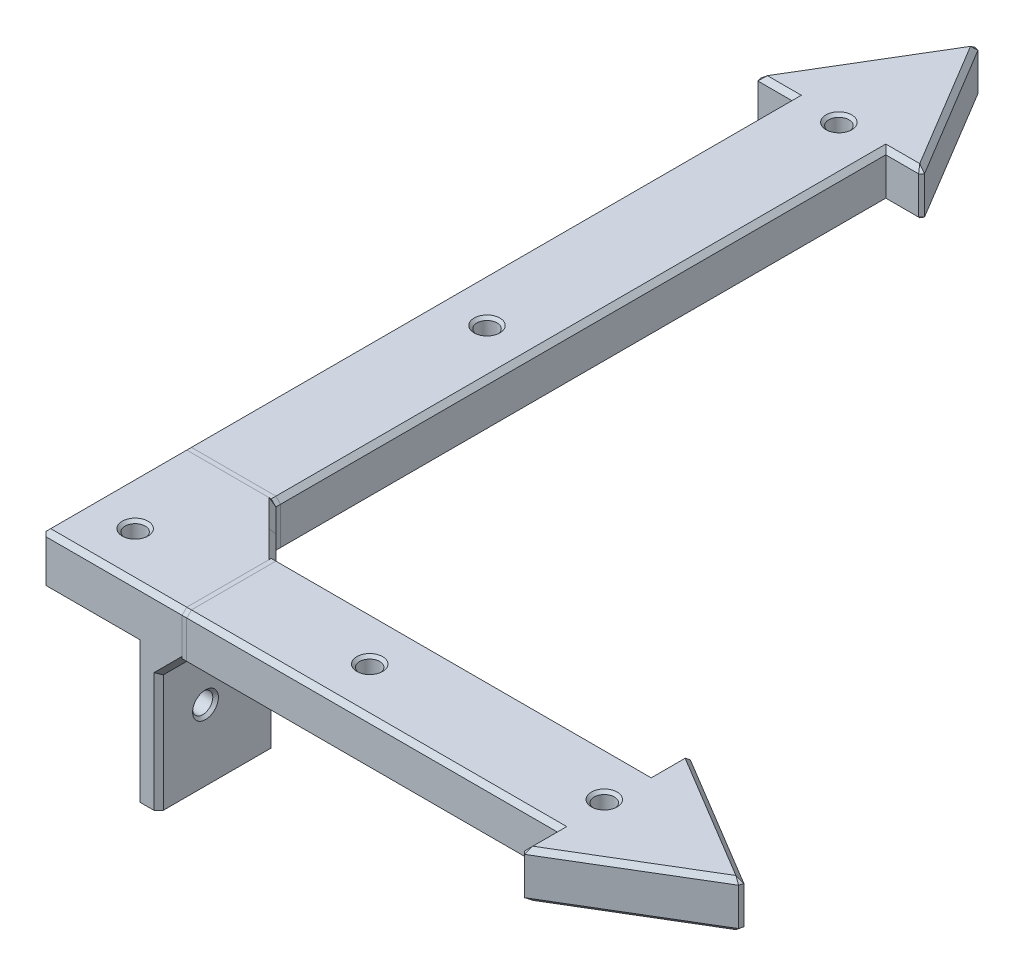
SolidWorks part; units mm, degrees
note: The reader was unsure of these and kept them because the rebuilt part matched: shared geometry of "Sketch3<3>", "Sketch9<2>".
ref_plane "Front Plane" through (0, 0, 0) normal (0, 0, 1) x (1, 0, 0)
ref_plane "Top Plane" through (0, 0, 0) normal (0, 1, 0) x (1, 0, 0)
ref_plane "Right Plane" through (0, 0, 0) normal (1, 0, 0) x (0, 0, -1)
sketch "Sketch1" plane through (0, 0, 0) normal (0, 1, 0) x (1, 0, 0)
  line L0 (0, 0) -> (100, 0) construction
  line L1 (0, 0) -> (0, 150) construction
  line L2 (10, 150) -> (10, 10)
  line L3 (10, 10) -> (100, 10)
  line L4 (100, -10) -> (-10, -10)
  line L5 (-10, -10) -> (-10, 150)
  line L6 (0, 150) -> (10, 150) construction
  line L7 (0, 150) -> (-10, 150) construction
  line L8 (100, 10) -> (100, 0) construction
  line L9 (100, 0) -> (100, -10) construction
  line L10 (0, 150) -> (0, 180) construction
  line L11 (0, 180) -> (18, 150)
  line L12 (18, 150) -> (10, 150)
  line L13 (-10, 150) -> (-18, 150)
  line L14 (-18, 150) -> (0, 180)
  line L15 (100, 0) -> (130, 0) construction
  line L16 (130, 0) -> (100, 18)
  line L17 (100, 18) -> (100, 10)
  line L18 (100, -10) -> (100, -18)
  line L19 (100, -18) -> (130, 0)
  dimension "D1" = 150
  dimension "D2" = 20
  dimension "D3" = 30
  dimension "D4" = 36
  dimension "D5" = 100
extrude "Boss-Extrude1" add sketch "Sketch1" along normal blind 10
sketch "Sketch2" plane through (0, 10, 0) normal (0, 1, 0) x (1, 0, 0)
  line L0 (0, 150) -> (0, 0) construction
  line L1 (0, 0) -> (100, 0) construction
  circle A0 centre (0, 150) radius 2.15
  circle A1 centre (100, 0) radius 2.15
  circle A2 centre (0, 0) radius 2.15
  circle A3 centre (0, 75) radius 2.15
  circle A4 centre (50, 0) radius 2.15
  dimension "D1" = 4.3
extrude "Cut-Extrude1" cut sketch "Sketch2" against normal through all
sketch "Sketch3" plane through (0, 0, 0) normal (0, -1, 0) x (1, 0, 0)
  line L5 (10, 10) -> (15, 10)
  line L16 (-10, 10) -> (10, 10) construction
  line L21 (-10, 10) -> (-10, -10) construction
  line L22 (-10, -10) -> (10, -10) construction
  line L23 (10, 10) -> (10, -10) construction
  line L24 (-10, 10) -> (10, -10) construction
  line L25 (-10, -10) -> (10, 10) construction
  line L26 (-10, 10) -> (100, 10) construction
  line L27 (15, 10) -> (15, -15)
  line L28 (15, -15) -> (-10, -15)
  line L29 (-10, -150) -> (-10, 10) construction
  line L30 (-10, -15) -> (-10, -10)
  line L31 (-10, -10) -> (10, -10)
  line L32 (10, -10) -> (10, 10)
  point P0 (0, 0)
  dimension "D1" = 5
extrude "Boss-Extrude5" add sketch "Sketch3" against normal up to surface (10 mm away) up to face at (0, 10, -147.85)
extrude "Boss-Extrude6" add sketch "Sketch3<3>" along normal blind 30
sketch "Sketch3<3>" plane through (0, 0, 0) normal (0, -1, 0) x (1, 0, 0) same geometry as "Sketch3"
sketch "Sketch4" plane through (0, 0, -10) normal (0, 0, 1) x (1, 0, 0)
  line L0 (-10, 0) -> (10, -30) construction
  circle A0 centre (0, -15) radius 2.15
  dimension "D1" = 4.3
extrude "Cut-Extrude2" cut sketch "Sketch4" against normal through all
sketch "Sketch5" plane through (10, 0, 0) normal (-1, 0, 0) x (0, 0, 1)
  line L0 (-10, 0) -> (10, -30) construction
  circle A0 centre (0, -15) radius 2.15
  dimension "D1" = 4.3
extrude "Cut-Extrude3" cut sketch "Sketch5" against normal through all
sketch "Sketch6" plane through (0, 0, 0) normal (0, -1, 0) x (1, 0, 0)
  circle A0 centre (0, 0) radius 5
  dimension "D1" = 10
extrude "Cut-Extrude4" cut sketch "Sketch6" against normal offset from surface (6 mm away) 4 up to face at (40, 10, -57.8571)
chamfer "Chamfer1" distance 5 angle 45 6 edges at (0, 0, -15) (12.5, 10, -15) (15, 10, -12.5) (10, 5, -15) (15, 5, -10) (15, 0, 0)
sketch "Sketch9" plane through (0, 10, 0) normal (0, 1, 0) x (1, 0, 0)
  line L0 (-10, 150) -> (-10, -10) construction
  line L1 (10, 20) -> (-10, 20)
  line L2 (10, 20) -> (10, 21)
  line L3 (10, 21) -> (-10, 21)
  line L4 (-10, 20) -> (-10, 21)
  line L5 (-10, -10) -> (100, -10) construction
  line L6 (20, 10) -> (21, 10)
  line L7 (20, 10) -> (20, -10)
  line L8 (20, -10) -> (21, -10)
  line L9 (21, 10) -> (21, -10)
  dimension "D1" = 1
extrude "Cut-Extrude5" cut sketch "Sketch9" against normal through all
extrude "Boss-Extrude7" add sketch "Sketch9<2>" against normal up to surface (10 mm away) separate body up to face at (0, 0, -147.85)
sketch "Sketch9<2>" plane through (0, 10, 0) normal (0, 1, 0) x (1, 0, 0) same geometry as "Sketch9"
chamfer "Chamfer2" distance 1 angle 45 15 edges at (-18, 5, -150) (-10, 0, -85.5) (-14, 0, -150) (-9, 0, -165) (9, 0, -165) (14, 0, -150) (10, 0, -85.5) (-10, 10, -85.5) (-14, 10, -150) (-9, 10, -165) (9, 10, -165) (14, 10, -150) (10, 10, -85.5) (18, 5, -150) (0, 5, -180)
chamfer "Chamfer3" distance 1 angle 45 3 edges at (10, 0, -20.5) (10, 10, -20.5) (-10, 10, -20.5)
chamfer "Chamfer4" distance 1 angle 45 4 edges at (5, 10, 10) (-10, 10, -5) (17.5, 10, -12.5) (12.5, 10, -17.5)
chamfer "Chamfer5" distance 1 angle 45 4 edges at (20.5, 0, -10) (20.5, 0, 10) (20.5, 10, -10) (20.5, 10, 10)
chamfer "Chamfer6" distance 1 angle 45 15 edges at (100, 0, -14) (100, 5, -18) (115, 0, -9) (130, 5, 0) (115, 0, 9) (100, 5, 18) (100, 0, 14) (60.5, 10, 10) (100, 10, 14) (115, 10, 9) (115, 10, -9) (100, 10, -14) (60.5, 10, -10) (60.5, 0, -10) (60.5, 0, 10)
chamfer "Chamfer7" distance 1 angle 45 8 edges at (-10, -2.5, -17.5) (-10, -15, -10) (17.5, -2.5, 10) (15, -17.5, 10) (-10, -17.5, -15) (15, -17.5, -15) (10, -15, 10) (-10, 4.5, 10)
sketch "Sketch10" plane through (0, 0, 0) normal (0, -1, 0) x (1, 0, 0)
  circle A0 centre (100, 0) radius 5
  circle A1 centre (0, -150) radius 5
  circle A2 centre (50, 0) radius 5
  circle A3 centre (0, -75) radius 5
  dimension "D1" = 10
extrude "Cut-Extrude6" cut sketch "Sketch10" against normal up to surface (6 mm away) up to face at (0, 6, 5)
chamfer "Chamfer8" distance 1 angle 45 1 edges at (0, 0, -155)
chamfer "Chamfer9" distance 1 angle 45 1 edges at (100, 0, -5)
chamfer "Chamfer10" distance 0.6 angle 45 2 edges at (-2.15, -15, -15) (15, -15, -2.15)
chamfer "Chamfer11" distance 1 angle 45 1 edges at (0, 0, -5)
chamfer "Chamfer12" distance 1 angle 45 1 edges at (-10, 0, -20.5)
chamfer "Chamfer13" distance 1 angle 45 1 edges at (50, 0, -5)
chamfer "Chamfer14" distance 1 angle 45 1 edges at (0, 0, -80)
chamfer "Chamfer15" distance 0.6 angle 45 2 edges at (50, 10, 2.15) (100, 10, 2.15)
chamfer "Chamfer16" distance 0.6 angle 45 1 edges at (0, 10, 2.15)
chamfer "Chamfer17" distance 0.6 angle 45 2 edges at (0, 10, -147.85) (0, 10, -72.85)
